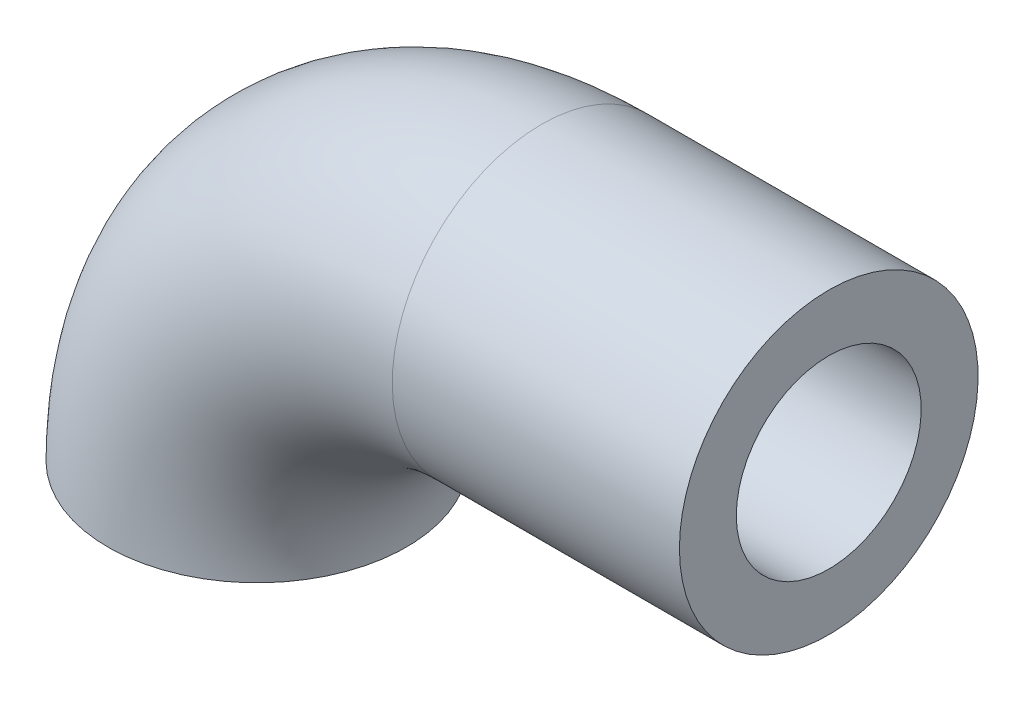
SolidWorks part; units mm, degrees
ref_plane "Front Plane" through (0, 0, 0) normal (0, 0, 1) x (1, 0, 0)
ref_plane "Top Plane" through (0, 0, 0) normal (0, 1, 0) x (1, 0, 0)
ref_plane "Right Plane" through (0, 0, 0) normal (1, 0, 0) x (0, 0, -1)
sketch "Sketch1" plane through (0, 0, 0) normal (0, 0, 1) x (1, 0, 0)
  line L0 (55, 0) -> (-55, 0) construction
  line L1 (0, -55) -> (0, 55) construction
  line L2 (10, 10) -> (20.0949, 10)
  arc A0 (0, 0) -> (10, 10) centre (10, 0) cw
  dimension "D1" = 10
  dimension "D2" = 10
sketch "Sketch2" plane through (0, 0, 0) normal (0, 1, 0) x (1, 0, 0)
  circle A0 centre (0, 0) radius 5.25
  circle A1 centre (0, 0) radius 3.25
  dimension "D1" = 6.5
  dimension "D2" = 2
sweep "Sweep1" add profiles "Sketch2" path "Sketch1"
